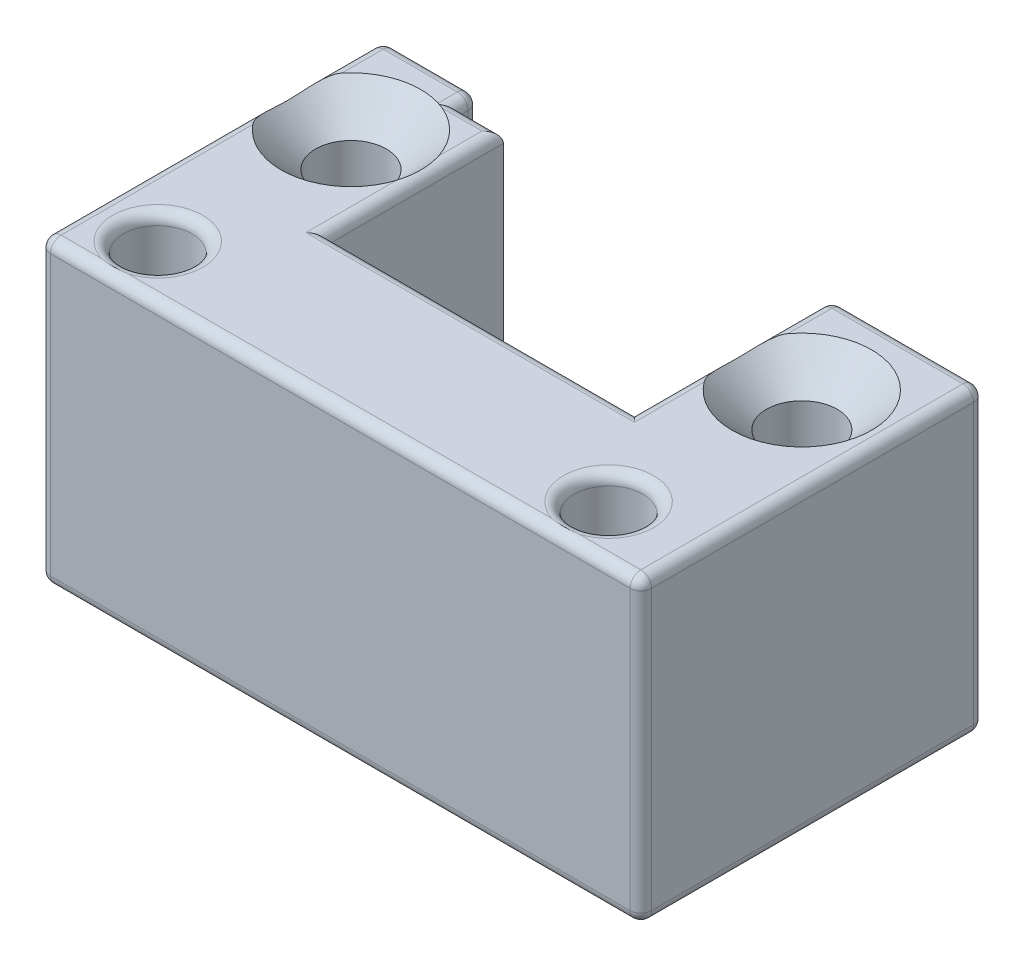
SolidWorks part; units mm, degrees
ref_plane "Front Plane" through (0, 0, 0) normal (0, 0, 1) x (1, 0, 0)
ref_plane "Top Plane" through (0, 0, 0) normal (0, 1, 0) x (1, 0, 0)
ref_plane "Right Plane" through (0, 0, 0) normal (1, 0, 0) x (0, 0, -1)
sketch "Sketch1" plane through (0, 0, 0) normal (0, 1, 0) x (1, 0, 0)
  line L0 (-3.25, 0) -> (3.25, 0) construction
  line L1 (6.4, 5) -> (-6.4, 5) construction
  line L2 (-14, -10) -> (14, -10)
  line L3 (-14, -10) -> (-14, 6)
  line L4 (-14, 6) -> (14, 6)
  line L5 (14, -10) -> (14, 6)
  line L6 (-11, -7.5) -> (10, -7.5) construction
  line L7 (0, 0) -> (0, -10) construction
  line L8 (-11, -7.5) -> (-11, 1.5) construction
  line L9 (-11, 1.5) -> (10, 1.5) construction
  line L10 (10, 1.5) -> (10, -7.5) construction
  circle A0 centre (3.25, 0) radius 0.85
  circle A1 centre (-3.25, 0) radius 0.85
  circle A2 centre (-11, -7.5) radius 1.6
  circle A3 centre (10, -7.5) radius 1.6
  circle A4 centre (-11, -7.5) radius 3 construction
  circle A5 centre (-11, 1.5) radius 1.6
  circle A6 centre (10, 1.5) radius 1.6
  circle A7 centre (-11, 1.5) radius 3 construction
  point P4 (0, 0)
  point P24 (9.546, -8.3811)
  point P25 (9.9063, 3.0023)
  point P26 (11.5416, -6)
  dimension "D1" = 1.7
  dimension "D2" = 6.5
  dimension "D6" = 3.2
  dimension "D8" = 6
  dimension "D9" = 9
  dimension "D10" = 2.5
  dimension "D3" = 16
  dimension "D4" = 28
  dimension "D5" = 1
  dimension "D7" = 21
  dimension "D11" = 4
extrude "Boss-Extrude1" add sketch "Sketch1" along normal blind 4
sketch "Sketch2" plane through (0, 4, 0) normal (0, 1, 0) x (1, 0, 0)
  line L0 (-9.5462, 6) -> (-9.5462, 5)
  line L1 (-7.4, -3.2) -> (6.9, -3.2)
  line L2 (6.9, -3.2) -> (6.9, 6)
  line L3 (-9.5462, 6) -> (-14, 6)
  line L4 (-14, 6) -> (-14, -10)
  line L5 (-14, -10) -> (14, -10)
  line L6 (14, -10) -> (14, 6)
  line L7 (14, 6) -> (6.9, 6)
  line L8 (14, -10) -> (14, 6) construction
  line L9 (14, 6) -> (-14, 6) construction
  line L10 (6.4, 1.3) -> (6.4, 5) construction
  line L11 (-14, 6) -> (-14, -10) construction
  line L13 (4.75, -1.2) -> (6.4, -1.2) construction
  line L14 (-9.5462, 5) -> (-7.4, 5)
  line L15 (-7.4, 5) -> (-7.4, -3.2)
  line L16 (-6.4, 5) -> (6.4, 5) construction
  line L17 (-6.4, 5) -> (-6.4, 1.3) construction
  circle A0 centre (-11, -7.5) radius 1.6 construction
  circle A1 centre (-11, -7.5) radius 1.6
  circle A2 centre (10, -7.5) radius 1.6 construction
  circle A3 centre (10, -7.5) radius 1.6
  circle A4 centre (10, 1.5) radius 1.6 construction
  circle A5 centre (-11, 1.5) radius 1.6 construction
  circle A6 centre (10, 1.5) radius 1.6
  circle A7 centre (-11, 1.5) radius 1.6
  dimension "D1" = 0.5
  dimension "D2" = 2
  dimension "D3" = 2
  dimension "D4" = 1
extrude "Boss-Extrude2" add sketch "Sketch2" along normal blind 10
fillet "Fillet1" radius 0.5 31 edges at (-14, 7, 10) (14, 7, 10) (10, 0, 9.1) (-3.25, 0, 0.85) (-14, 0, 2) (0, 0, 10) (14, 0, 2) (3.25, 0, 0.85) (-11, 0, 9.1) (14, 7, -6) (6.9, 9, -6) (-1.3231, 4, -6) (-9.5462, 9, -6) (-14, 7, -6) (0, 0, -6) (10, 14, 9.1) (-9.5462, 14, -5.5) (-8.4731, 14, -5) (-7.4, 14, -0.9) (-0.25, 14, 3.2) (6.9, 14, -1.4) (10.45, 14, -6) (14, 14, 2) (0, 14, 10) (-14, 14, 2) (-11.7731, 14, -6) (-11, 14, 9.1) (10, 0, 0.1) (-11, 0, 0.1) (-11, 14, 0.1) (10, 14, 0.1)
hole_wizard "CSK for M5 Flat Head Machine Screw1" positions "3DSketch1" profile "Sketch3" countersink size "M5" standard "ANSI Metric" end condition through all
sketch3d "3DSketch1"
  line L0 (10, 12.3079, -1.5) -> (10, 15.8843, -1.5) construction
  line L1 (-11, 12.3079, -1.5) -> (-11, 15.8843, -1.5) construction
  point P0 (10, 14, -1.5)
  point P4 (-11, 14, -1.5)
sketch "Sketch3" plane through (10, 14, -1.5) normal (1, 0, 0) x (0, 0, 1)
  line L0 (0, 0) -> (0, 14)
  line L1 (0, 14) -> (1.65, 14)
  line L2 (1.65, 14) -> (1.65, 1.6)
  line L3 (1.65, 1.6) -> (3.25, 0)
  line L5 (3.25, 0) -> (0, 0)
  line L6 (-1.65, 1.6) -> (-3.25, 0) construction
  line L11 (0, -6.35) -> (0, 107.95) construction
  dimension "Thru Hole Dia." = 3.3
  dimension "Thru Hole Depth" = 14
  dimension "Near C'Sink Dia." = 6.5
  dimension "Near C'Sink Angle" = 90
